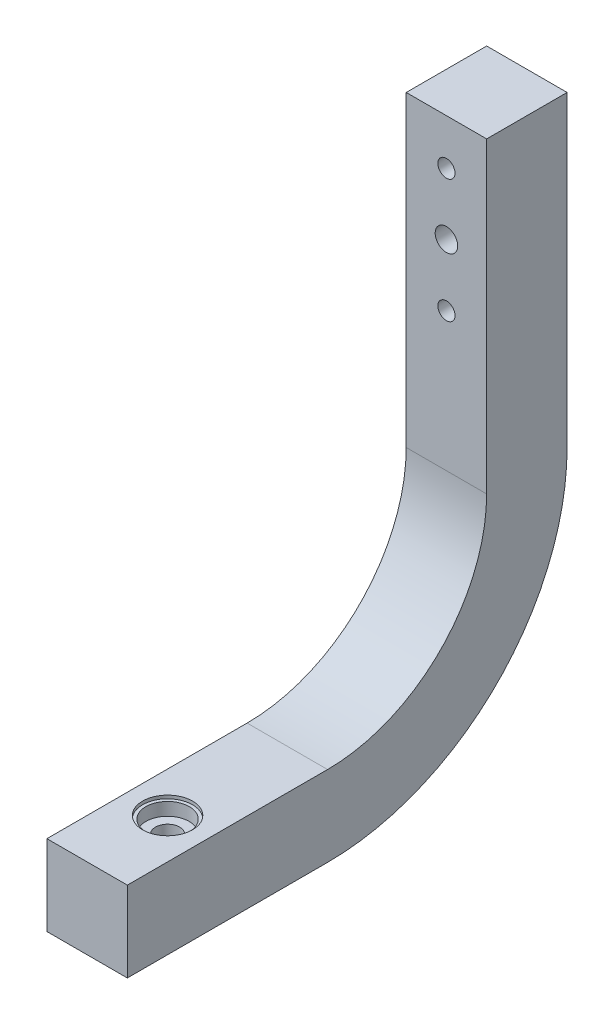
SolidWorks part; units mm, degrees
ref_plane "Front Plane" through (0, 0, 0) normal (0, 0, 1) x (1, 0, 0)
ref_plane "Top Plane" through (0, 0, 0) normal (0, 1, 0) x (1, 0, 0)
ref_plane "Right Plane" through (0, 0, 0) normal (1, 0, 0) x (0, 0, -1)
ref_axis "Z" through (0, 0, 86.1) along (0, 0, -1)
sketch "Sketch1" plane through (0, 0, 0) normal (1, 0, 0) x (0, 0, -1)
  line L0 (-15, 20) -> (0, 20)
  line L1 (0, 20) -> (0, -37.3333)
  line L2 (0, -32) -> (-50, -82) construction
  line L3 (-44.6667, -82) -> (-67, -82)
  line L4 (-67, -82) -> (-67, -67) construction
  line L5 (-67, -67) -> (-44.6667, -67)
  line L6 (-56.2132, -67) -> (-15, -25.7868) construction
  line L7 (-15, -37.3333) -> (-15, 20)
  line L8 (-35.6066, -46.3934) -> (-25, -57) construction
  line L9 (-44.6667, -67) -> (-56.2132, -67) construction
  line L10 (-67, -67) -> (-82, -67)
  line L11 (-67, -67) -> (-67, -82) construction
  line L12 (-67, -82) -> (-82, -82)
  line L13 (-82, -67) -> (-82, -82)
  line L14 (-15, -25.7868) -> (-15, -37.3333) construction
  line L15 (0, -37.3333) -> (0, -32) construction
  line L16 (-50, -82) -> (-44.6667, -82) construction
  arc A0 (-44.6667, -67) -> (-15, -37.3333) centre (-44.6667, -37.3333) ccw
  arc A1 (-44.6667, -82) -> (0, -37.3333) centre (-44.6667, -37.3333) ccw
  dimension "D1" = 15
  dimension "D2" = 67
  dimension "D3" = 82
  dimension "D4" = 20
  dimension "D5" = 135
  dimension "D6" = 50
  dimension "D7" = 15
  dimension "D8" = 22.3333
extrude "Boss-Extrude1" add sketch "Sketch1" along normal blind 7.5 and the other way blind 7.5
sketch "Sketch3" plane through (0, -67, 0) normal (0, 1, 0) x (1, 0, 0)
  line L0 (-8.25, 0) -> (8.25, 0) construction
  line L1 (0, -45.1) -> (0, 45.1) construction
  circle A0 centre (0, -67) radius 2.25
  dimension "D2" = 4.5
  dimension "D1" = 67
extrude "Cut-Extrude1" cut sketch "Sketch3" against normal through all
sketch "Sketch4" plane through (0, 0, 15) normal (0, 0, 1) x (1, 0, 0)
  line L0 (0, -11.5) -> (0, 11.5) construction
  circle A0 centre (0, 0) radius 2.1
  circle A1 centre (0, 11.5) radius 1.6
  circle A2 centre (0, -11.5) radius 1.6
  dimension "D1" = 4.2
  dimension "D3" = 3.2
  dimension "D2" = 23
extrude "Cut-Extrude2" cut sketch "Sketch4" against normal through all both and the other way through all
ref_axis "Axis1" through (0, -52.3642, 67) along (0, 1, 0)
sketch "Sketch5" plane through (0, 0, 0) normal (1, 0, 0) x (0, 0, -1)
  line L0 (-62.95, -79) -> (-62.95, -81.4)
  line L1 (-62.95, -81.4) -> (-62.35, -81.4)
  line L2 (-62.35, -81.4) -> (-62.35, -82)
  line L3 (-62.35, -82) -> (-67, -82)
  line L4 (-67, -82) -> (-67, -79)
  line L5 (-67, -79) -> (-62.95, -79)
  line L6 (-67, -74.5) -> (-67, -90.6731) construction
  line L7 (-67, -74.5) -> (-82, -74.5) construction
  line L8 (-67, -70) -> (-62.95, -70)
  line L9 (-67, -67) -> (-67, -70)
  line L10 (-62.35, -67) -> (-67, -67)
  line L11 (-62.35, -67.6) -> (-62.35, -67)
  line L12 (-62.95, -67.6) -> (-62.35, -67.6)
  line L13 (-62.95, -70) -> (-62.95, -67.6)
  line L16 (-67, -52.3642) -> (-67, -36.7401) construction
  line L17 (-82, -67) -> (-82, -82) construction
  line L18 (-67, -67) -> (-44.6667, -67) construction
  point P15 (-84.9322, -76.3954)
  point P16 (-90.3733, -70.8282)
  dimension "D2" = 4.65
  dimension "D3" = 3
  dimension "D4" = 8.1
revolve "Cut-Revolve1" cut sketch "Sketch5" angle 360 about axis through (0, -52.3642, 67) along (0, 1, 0)
equation "\"rbracket-width\"= \"L2Thickness\""
equation "\"D1@Boss-Extrude1\"=\"rbracket-width\"/2"
equation "\"D2@Boss-Extrude1\"=\"rbracket-width\"/2"
equation "\"EyeCaptureRadius\"= ( \"EyeDiameter\" + \"EyeClearance\" ) / 2"
equation "\"rbracket_planetocenterline_dist\"= \"BasePlaneDistance\""
equation "\"D2@Sketch1\"=\"rbracket_planetocenterline_dist\""
equation "\"EyeDiameter\" = 100"
equation "\"BasePlaneDistance\" = \"EyeDiameter\"/2+\"L2Thickness\"+\"EyeClearance\""
equation "\"EyeClearance\" = 2"
equation "\"D1@Sketch1\"=\"rbracket-width\""
equation "\"D3@Sketch1\"=(\"EyeDiameter\"+\"EyeClearance\"+\"EyeClearance\")/2 + \"L2Thickness\" + \"rbracket-width\""
equation "\"D6@Sketch1\"=\"EyeDiameter\"/2"
equation "\"D7@Sketch1\"=\"rbracket-width\""
equation "\"D1@Sketch3\"=\"BasePlaneDistance\""
equation "\"L2Thickness\" = 3.75 * \"shaft_diameter\""
equation "\"D8@Sketch1\"=\"rbracket_planetocenterline_dist\"/3"
equation "\"BearingFlangeOD\"= 7.5"
equation "\"BearingFlangeThickness\"= 0.75"
equation "\"BearingHousingID\"=4.5"
equation "\"BearingDepth\"= 6"
equation "\"PrinterFilamentThickness\"= 0.1"
equation "\"ApplyPrinterOffsets\"= 1"
equation "\"L2_ID\" = 20"
equation "\"vx\" = 0"
equation "\"vy\" = 0"
equation "\"vz\" = 100"
equation "\"parametric_end\" = 1"
equation "\"Rw_3_xx\" = -(\"vz\")/sqr((\"vx\")^2 + (\"vz\")^2)"
equation "\"Rw_3_xy\" = 0"
equation "\"Rw_3_xz\" = (\"vx\")/sqr((\"vx\")^2 + (\"vz\")^2)"
equation "\"Rw_3_zx\" = (\"vx\")/sqr((\"vx\")^2 + (\"vy\")^2 + (\"vz\")^2)"
equation "\"Rw_3_zy\" = (\"vy\")/sqr((\"vx\")^2 + (\"vy\")^2 + (\"vz\")^2)"
equation "\"Rw_3_zz\" = (\"vz\")/sqr((\"vx\")^2 + (\"vy\")^2 + (\"vz\")^2)"
equation "\"Rw_3_yx\" = (\"vx\")*(\"vy\")/sqr((\"vx\")^4 + (\"vx\")^2*(\"vy\")^2 + 2*(\"vx\")^2*(\"vz\")^2 + (\"vy\")^2*(\"vz\")^2 + (\"vz\")^4)"
equation "\"Rw_3_yy\" = -sqr((\"vx\")^2 + (\"vz\")^2)/sqr((\"vx\")^2 + (\"vy\")^2 + (\"vz\")^2)"
equation "\"Rw_3_yz\" = (\"vy\")*(\"vz\")/sqr((\"vx\")^4 + (\"vx\")^2*(\"vy\")^2 + 2*(\"vx\")^2*(\"vz\")^2 + (\"vy\")^2*(\"vz\")^2 + (\"vz\")^4)"
equation "\"O2Targx\" = -\"BasePlaneDistance\"*(\"vx\")*(\"vy\")/sqr((\"vx\")^4 + (\"vx\")^2*(\"vy\")^2 + 2*(\"vx\")^2*(\"vz\")^2 + (\"vy\")^2*(\"vz\")^2 + (\"vz\")^4)"
equation "\"O2Targy\" = \"BasePlaneDistance\"*sqr((\"vx\")^2 + (\"vz\")^2)/sqr((\"vx\")^2 + (\"vy\")^2 + (\"vz\")^2)"
equation "\"O2Targz\" = -\"BasePlaneDistance\"*(\"vy\")*(\"vz\")/sqr((\"vx\")^4 + (\"vx\")^2*(\"vy\")^2 + 2*(\"vx\")^2*(\"vz\")^2 + (\"vy\")^2*(\"vz\")^2 + (\"vz\")^4)"
equation "\"O2Targx_0\" = -(\"BasePlaneDistance\")*sqr((\"vx\")^2 + (\"vz\")^2)/sqr((\"vx\")^2 + (\"vy\")^2 + (\"vz\")^2)"
equation "\"O2Targy_0\" = -(\"BasePlaneDistance\")*(\"vy\")*(\"vz\")/sqr((\"vx\")^4 + (\"vx\")^2*(\"vy\")^2 + 2*(\"vx\")^2*(\"vz\")^2 + (\"vy\")^2*(\"vz\")^2 + (\"vz\")^4)"
equation "\"O2Targz_0\" = (\"BasePlaneDistance\")*(\"vx\")*(\"vy\")/sqr((\"vx\")^4 + (\"vx\")^2*(\"vy\")^2 + 2*(\"vx\")^2*(\"vz\")^2 + (\"vy\")^2*(\"vz\")^2 + (\"vz\")^4) + (\"BasePlaneDistance\")"
equation "\"theta2_s1\" = arcsin(((\"BasePlaneDistance\") - (\"O2Targz_0\"))/(\"BasePlaneDistance\")) + pi"
equation "\"theta2_s2\" = -arcsin(((\"BasePlaneDistance\") - (\"O2Targz_0\"))/(\"BasePlaneDistance\"))"
equation "\"theta1_s1\" = arcsin((\"O2Targy_0\")/((\"BasePlaneDistance\")*cos((\"Theta2\")))) + pi"
equation "\"theta1_s2\" = -arcsin((\"O2Targy_0\")/((\"BasePlaneDistance\")*cos((\"Theta2\"))))"
equation "\"theta1_s3\" = -arccos(-(\"O2Targx_0\")/((\"BasePlaneDistance\")*cos((\"Theta2\")))) + 2*pi"
equation "\"theta1_s4\" = arccos(-(\"O2Targx_0\")/((\"BasePlaneDistance\")*cos((\"Theta2\"))))"
equation "\"Theta1\" = \"theta1_s2\" 'so far, theta1_s1 and theta1_s4 have agreed, and they agree with the sw constraint solver"
equation "\"Theta2\" = \"theta2_s2\""
equation "\"o2_x\" = -(\"BasePlaneDistance\")*cos((\"Theta1\"))*cos((\"Theta2\"))"
equation "\"o2_y\" = -(\"BasePlaneDistance\")*sin((\"Theta1\"))*cos((\"Theta2\"))"
equation "\"o2_z\" = (\"BasePlaneDistance\")*(sin((\"Theta2\")) + 1)"
equation "\"o1_x\" = (\"BasePlaneDistance\")*sin((\"Theta1\"))"
equation "\"o1_y\" = -(\"BasePlaneDistance\")*cos((\"Theta1\"))"
equation "\"o1_z\" = (\"BasePlaneDistance\")"
equation "\"Actuator1_Theta\" = atn(\"vx\"/\"vz\") 'ik solution for the single link joint"
equation "\"Actuator2_Theta\" = \"Theta1\"  'ik solution for the double link joint"
equation "\"MotorBaseThickness\" = 3 "
equation "\"BaseThickness\" = 3 "
equation "\"EncoderToMagnetAirgap\" = 1 'Encoder to magnet airgap"
equation "\"EncoderHeight\" = 1.192  'Height of the encoder"
equation "\"MagnetThickness\" = 0.5  'Magnet thickness"
equation "\"pcb_thickness\" = 1.6  'Thickness of the PCB"
equation "\"pcb_outer_diameter\" = 32 'the OD of the pcb"
equation "\"shaft_diameter\" = 4"
equation "\"D2@Sketch3\"=\"shaft_diameter\"*1.125"
equation "\"D2@Sketch5\"=\"ApplyPrinterOffsets\"*\"PrinterFilamentThickness\"/2+4.6"
equation "\"D4@Sketch5\"=\"ApplyPrinterOffsets\"*\"PrinterFilamentThickness\"+8"
